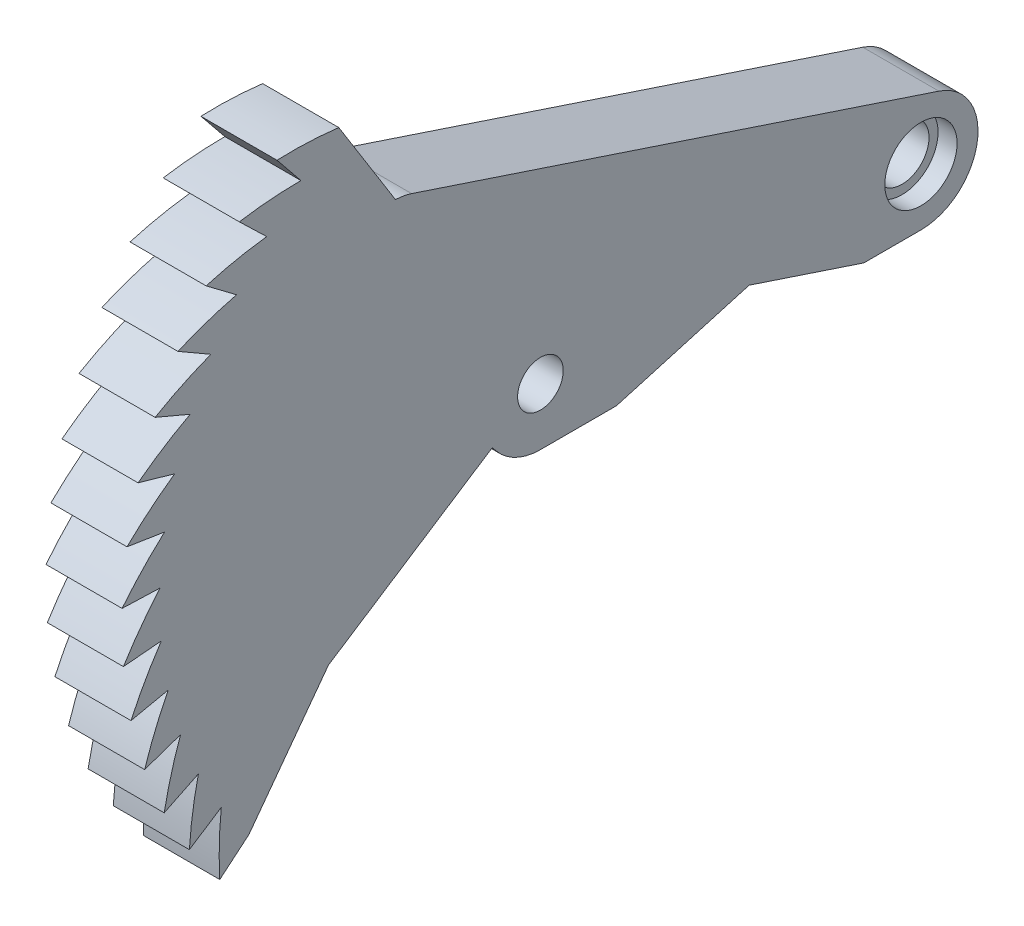
SolidWorks part; units mm, degrees
note: The reader was unsure of these and kept them because the rebuilt part matched: shared geometry of "草图4<3>", "草图1<2>".
material "环氧树脂,未充填"
ref_plane "前视基准面" through (0, 0, 0) normal (0, 0, 1) x (1, 0, 0)
ref_plane "上视基准面" through (0, 0, 0) normal (0, 1, 0) x (1, 0, 0)
ref_plane "右视基准面" through (0, 0, 0) normal (1, 0, 0) x (0, 0, -1)
other "Configuration Table"
sketch "草图1" plane through (0, 0, 0) normal (1, 0, 0) x (0, 0, -1)
  line L0 (0, 0) -> (20, 0) construction
  line L1 (20, 0) -> (-7.7135, 9.1925) construction
  line L2 (-7.7135, 9.1925) -> (0, 0) construction
  line L3 (0, -3) -> (20, -3)
  line L4 (20.9445, 2.8474) -> (-6.769, 12.04)
  line L5 (-10.0116, 7.2642) -> (-2.2981, -1.9284)
  circle A0 centre (0, 0) radius 1.2
  circle A1 centre (20, 0) radius 1.425
  circle A2 centre (-7.7135, 9.1925) radius 1.2
  arc A3 (20, -3) -> (20.9445, 2.8474) centre (20, 0) ccw
  arc A4 (-6.769, 12.04) -> (-10.0116, 7.2642) centre (-7.7135, 9.1925) ccw
  arc A5 (-2.2981, -1.9284) -> (0, -3) centre (0, 0) ccw
  dimension "D4" = 2.85
  dimension "D5" = 3
  dimension "D6" = 2.4
  dimension "D7" = 2.4
  dimension "D1" = 130
  dimension "D2" = 20
  dimension "D3" = 12
extrude "凸台-拉伸1" add sketch "草图1" along normal mid plane 4
sketch "草图3" plane through (2, 0, 0) normal (1, 0, 0) x (0, 0, -1)
  circle A0 centre (20, 0) radius 1.9
  dimension "D1" = 3.8
extrude "切除-拉伸2" cut sketch "草图3" against normal blind 1
sketch "草图4" plane through (0, 0, 0) normal (1, 0, 0) x (0, 0, -1)
  line L1 (0, 0) -> (-16.7734, -10.8928)
  line L2 (0, 0) -> (50000, 0) construction
  line L3 (-16.7734, -10.8928) -> (-18.4508, -11.9821)
  line L4 (-17.9759, -8.7674) -> (0, 0) construction
  line L5 (-17.9759, -8.7674) -> (-19.7735, -9.6442)
  line L6 (-18.9104, -6.5114) -> (-20.8014, -7.1625)
  line L7 (-19.563, -4.1582) -> (-21.5192, -4.5741)
  line L8 (-19.9239, -1.7431) -> (-21.9163, -1.9174)
  line L9 (-19.9878, 0.698) -> (-21.9866, 0.7678)
  line L10 (-19.7538, 3.1287) -> (-21.7291, 3.4416)
  line L11 (-19.2252, 5.5127) -> (-21.1478, 6.064)
  line L12 (-18.4101, 7.8146) -> (-20.2511, 8.5961)
  line L13 (-17.3205, 10) -> (-19.0526, 11)
  line L14 (-15.9727, 12.0363) -> (-17.57, 13.2399)
  line L15 (-14.3868, 13.8932) -> (-15.8255, 15.2825)
  line L16 (-12.5864, 15.5429) -> (-13.845, 17.0972)
  line L17 (-10.5984, 16.961) -> (-11.6582, 18.6571)
  line L18 (-8.4524, 18.1262) -> (-9.2976, 19.9388)
  line L19 (0, 0) -> (-10.5984, 16.961)
  line L29 (-18.9104, -6.5114) -> (0, 0) construction
  line L30 (-11.1451, -7.2377) -> (-15.3209, -12.8558)
  line L31 (-15.3209, -12.8558) -> (0, 0) construction
  arc A0 (-12.5864, 15.5429) -> (-16.7734, -10.8928) centre (0, 0) ccw
  arc A1 (-18.4508, -11.9821) -> (-17.9759, -8.7674) centre (1.5066, -13.2878) cw
  arc A2 (-19.7735, -9.6442) -> (-18.9104, -6.5114) centre (-0.124, -13.3724) cw
  arc A3 (-20.8014, -7.1625) -> (-19.563, -4.1582) centre (-1.7528, -13.2576) cw
  arc A4 (-21.5192, -4.5741) -> (-19.9239, -1.7431) centre (-3.3554, -12.9451) cw
  arc A5 (-21.9163, -1.9174) -> (-19.9878, 0.698) centre (-4.908, -12.4397) cw
  arc A6 (-21.9866, 0.7678) -> (-19.7538, 3.1287) centre (-6.3875, -11.7489) cw
  arc A7 (-21.7291, 3.4416) -> (-19.2252, 5.5127) centre (-7.7717, -10.8829) cw
  arc A8 (-21.1478, 6.064) -> (-18.4101, 7.8146) centre (-9.04, -9.8546) cw
  arc A9 (-20.2511, 8.5961) -> (-17.3205, 10) centre (-10.1736, -8.6795) cw
  arc A10 (-19.0526, 11) -> (-15.9727, 12.0363) centre (-11.1555, -7.3749) cw
  arc A11 (-17.57, 13.2399) -> (-14.3868, 13.8932) centre (-11.9712, -5.9604) cw
  arc A12 (-15.8255, 15.2825) -> (-12.5864, 15.5429) centre (-12.6083, -4.4571) cw
  arc A13 (-13.845, 17.0972) -> (-10.5984, 16.961) centre (-13.0575, -2.8873) cw
  arc A14 (-11.6582, 18.6571) -> (-8.4524, 18.1262) centre (-13.3121, -1.2744) cw
  arc A15 (-9.2976, 19.9388) -> (-6.1803, 19.0211) centre (-13.3682, 0.3574) cw
  arc A16 (-10.5984, 16.961) -> (-16.7734, -10.8928) centre (0, 0) ccw
  arc A26 (-16.7734, -10.8928) -> (-15.3209, -12.8558) centre (0, 0) ccw
  point P112 (0, 0)
  dimension "D6" = 20
  dimension "D1" = 7
  dimension "D2" = 33
  dimension "D3" = 20
  dimension "D4" = 2
  dimension "D5" = 7
  dimension "D8" = 7
  dimension "D9" = 91
  dimension "D7" = 15
extrude "凸台-拉伸2" add sketch "草图4" along normal mid plane 4
extrude "凸台-拉伸3" add sketch "草图4<3>" along normal mid plane 4 contours A1 L3 A0
sketch "草图4<3>" plane through (0, 0, 0) normal (1, 0, 0) x (0, 0, -1) same geometry as "草图4"
pattern_circular "阵列(圆周)1" count 13 every 7 about axis through (0, 0, 0) along (1, 0, 0) of "凸台-拉伸3"
pattern_circular "阵列(圆周)2" count 2 every 7 about axis through (0, 0, 0) along (1, 0, 0) of "凸台-拉伸3"
extrude "切除-拉伸3" cut sketch "草图1<2>" against normal mid plane 4 contours A0
sketch "草图1<2>" plane through (0, 0, 0) normal (1, 0, 0) x (0, 0, -1) same geometry as "草图1"
sketch "草图5" plane through (0, 0, 0) normal (1, 0, 0) x (0, 0, -1)
  line L0 (4, -3) -> (10.9704, -1)
  line L1 (0, -3) -> (20, -3) construction
  line L2 (10.9704, -1) -> (17, -3)
  line L3 (17, -3) -> (4, -3)
  line L4 (20.9445, 2.8474) -> (-6.769, 12.04) construction
  circle A0 centre (20, 0) radius 1.425 construction
  dimension "D1" = 4
  dimension "D2" = 3
  dimension "D3" = 2
extrude "切除-拉伸4" cut sketch "草图5" against normal through all and the other way through all
sketch "草图6" plane through (2, 0, 0) normal (1, 0, 0) x (0, 0, -1)
  line L0 (-15.3209, -12.8558) -> (-17.7071, -16.0661)
  line L1 (-17.7071, -16.0661) -> (-1.6555, -27.997)
  line L2 (-1.6555, -27.997) -> (0.7307, -24.7867)
  line L3 (0.7307, -24.7867) -> (-15.3209, -12.8558)
  line L4 (-11.1451, -7.2377) -> (-15.3209, -12.8558) construction
  dimension "D1" = 20
  dimension "D2" = 4
  dimension "D3" = 20
extrude "切除-拉伸5" [suppressed] cut sketch "草图6" against normal through all
sketch "草图7" plane through (0, 0, 0) normal (1, 0, 0) x (0, 0, -1)
  circle A0 centre (20, 0) radius 3
  circle A1 centre (20, 0) radius 0.85
  dimension "D1" = 1.7
  dimension "D2" = 6
extrude "凸台-拉伸4" [suppressed] add sketch "草图7" along normal mid plane 4 contours A0 A1
